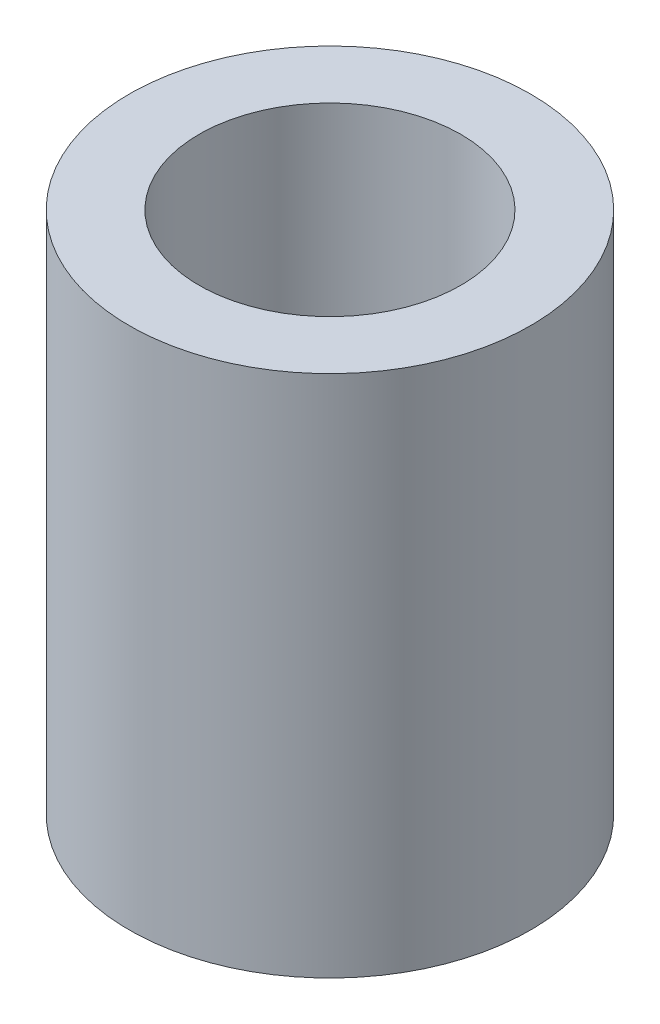
SolidWorks part; units mm, degrees
ref_plane "Front Plane" through (0, 0, 0) normal (0, 0, 1) x (1, 0, 0)
ref_plane "Top Plane" through (0, 0, 0) normal (0, 1, 0) x (1, 0, 0)
ref_plane "Right Plane" through (0, 0, 0) normal (1, 0, 0) x (0, 0, -1)
sketch "Croquis1" plane through (0, 0, 0) normal (1, 0, 0) x (0, 0, -1)
  line L0 (0, 0) -> (0, 98.5333) construction
  line L1 (15, 0) -> (23, 0)
  line L2 (15, 0) -> (15, 60)
  line L3 (15, 60) -> (23, 60)
  line L4 (23, 0) -> (23, 60)
  dimension "D1" = 30
  dimension "D2" = 8
  dimension "D3" = 60
revolve "Revolución1" add sketch "Croquis1" angle 360 about L0
equation "\"OD\"=24.2963"
equation "\"Pared\"=5.13824"
equation "\"Altura\"=66.7971"
